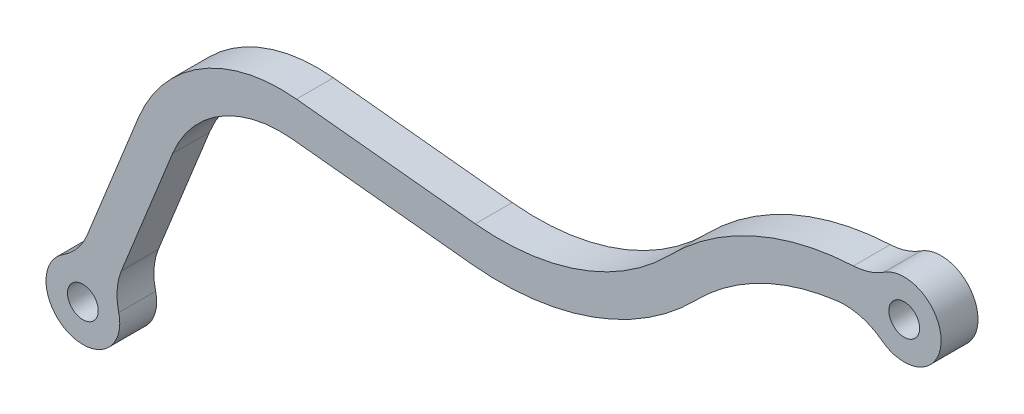
SolidWorks part; units mm, degrees
note: The reader was unsure of these and kept them because the rebuilt part matched: shared geometry of "Sketch1<3>".
ref_plane "Спереди" through (0, 0, 0) normal (0, 0, 1) x (1, 0, 0)
ref_plane "Сверху" through (0, 0, 0) normal (0, 1, 0) x (1, 0, 0)
ref_plane "Справа" through (0, 0, 0) normal (1, 0, 0) x (0, 0, -1)
other "Configuration Table"
sketch "Sketch1" plane through (0, 0, 0) normal (0, 0, 1) x (1, 0, 0)
  line L0 (32.4057, 20.4925) -> (17.8642, 22.0056)
  line L1 (30.9283, 23.6624) -> (21.4794, 24.6456) construction
  line L2 (6.5582, 15.1948) -> (0.6537, 0.5285)
  circle A0 centre (0.6537, 0.5285) radius 3 construction
  circle A1 centre (0.6537, 0.5285) radius 3
  arc A2 (70.3356, 33.4669) -> (64.5425, 31.9047) centre (67.439, 32.6858) ccw construction
  arc A3 (70.3356, 33.4669) -> (64.5425, 31.9047) centre (67.439, 32.6858) ccw construction
  circle A4 centre (67.439, 32.6858) radius 3
  arc A5 (32.4057, 20.4925) -> (49.4463, 26.6411) centre (34.5612, 41.2068) ccw
  arc A6 (49.4463, 26.6411) -> (67.439, 32.6858) centre (64.3611, 12.0465) cw
  arc A7 (17.8642, 22.0056) -> (6.5582, 15.1948) centre (16.7294, 11.1) ccw
  arc A8 (27.3821, 20.9871) -> (24.3988, 21.2975) centre (25.8934, 21.1702) ccw construction
  arc A9 (27.3821, 20.9871) -> (24.3988, 21.2975) centre (25.8934, 21.1702) ccw construction
  arc A11 (59.7739, 31.0929) -> (49.1568, 26.3408) centre (60.1381, 16.0427) ccw construction
extrude "Extrude-Thin1" add sketch "Sketch1" along normal blind 3 thin contours A5 L0 | L0 A7 L2
extrude "Boss-Extrude1" add sketch "Sketch1<3>" along normal through all
sketch "Sketch1<3>" plane through (0, 0, 0) normal (0, 0, 1) x (1, 0, 0) same geometry as "Sketch1"
fillet "Fillet1" radius 5 4 edges at (3.0154, 2.3784, 1.5) (0.2325, 3.4988, 1.5) (64.7235, 31.4106, 1.5) (64.9808, 34.4054, 1.5)
hole_wizard "Ø2.5mm Dowel Hole1" positions "Sketch2" profile "Sketch3" hole size "Ø2.5" standard "ISO" end condition through all
sketch "Sketch2" plane through (0, 0, 3) normal (0, 0, 1) x (1, 0, 0)
  arc A0 (65.6285, 30.2937) -> (65.7983, 35.1973) centre (67.439, 32.6858) ccw construction
  arc A1 (65.6285, 30.2937) -> (65.7983, 35.1973) centre (67.439, 32.6858) ccw
  point P0 (67.439, 32.6858)
  point P2 (0.6537, 0.5285)
sketch "Sketch3" plane through (67.439, 32.6858, 3) normal (1, 0, 0) x (0, -1, 0)
  line L0 (0, 0) -> (0, 3)
  line L1 (0, 3) -> (1.25, 3)
  line L2 (1.25, 3) -> (1.25, 0)
  line L5 (1.25, 0) -> (0, 0)
  line L11 (0, -6.35) -> (0, 107.95) construction
  dimension "Thru Hole Dia." = 2.5
  dimension "Thru Hole Depth" = 3
